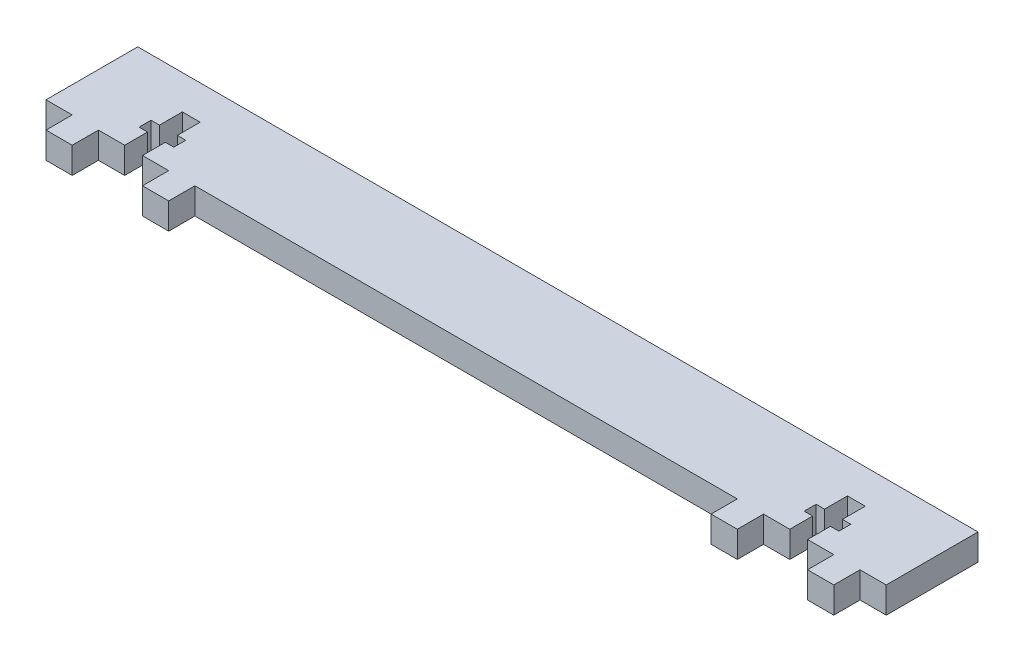
SolidWorks part; units mm, degrees
ref_plane "Front Plane" through (0, 0, 0) normal (0, 0, 1) x (1, 0, 0)
ref_plane "Top Plane" through (0, 0, 0) normal (0, 1, 0) x (1, 0, 0)
ref_plane "Right Plane" through (0, 0, 0) normal (1, 0, 0) x (0, 0, -1)
sketch "Sketch1" plane through (0, 0, 0) normal (0, 1, 0) x (1, 0, 0)
  line L0 (0, 11.1125) -> (0, -11.1125) construction
  line L1 (-101.7524, -11.1125) -> (-95.4024, -11.1125)
  line L2 (-101.7524, -11.1125) -> (-101.7524, 11.1125)
  line L3 (-101.7524, 11.1125) -> (101.7524, 11.1125)
  line L4 (101.7524, -11.1125) -> (101.7524, 11.1125)
  line L5 (-101.7524, -11.1125) -> (101.7524, 11.1125) construction
  line L6 (-101.7524, 11.1125) -> (101.7524, -11.1125) construction
  line L7 (-65.6844, -11.1125) -> (65.6844, -11.1125)
  line L8 (101.7524, -11.1125) -> (95.4024, -11.1125)
  point P0 (0, 0)
  line B0 (-89.0524, -11.1125) -> (-89.0524, -17.4625)
  line B1 (-89.0524, -17.4625) -> (-95.4024, -17.4625)
  line B2 (-95.4024, -17.4625) -> (-95.4024, -11.1125)
  line B3 (-82.7024, -11.1125) -> (-82.7024, -5.5775)
  line B4 (-82.7024, -5.5775) -> (-84.7434, -5.5775)
  line B5 (-84.7434, -5.5775) -> (-84.7434, -2.6775)
  line B6 (-84.7434, -2.6775) -> (-82.7024, -2.6775)
  line B7 (-82.7024, -2.6775) -> (-82.7024, 2.8575)
  line B8 (-82.7024, 2.8575) -> (-78.3844, 2.8575)
  line B9 (-78.3844, 2.8575) -> (-78.3844, -2.6775)
  line B10 (-78.3844, -2.6775) -> (-76.3434, -2.6775)
  line B11 (-76.3434, -2.6775) -> (-76.3434, -5.5775)
  line B12 (-76.3434, -5.5775) -> (-78.3844, -5.5775)
  line B13 (-78.3844, -5.5775) -> (-78.3844, -11.1125)
  line B14 (-80.5434, 2.8575) -> (-80.5434, -11.1125) construction
  line B15 (-72.0344, -11.1125) -> (-78.3844, -11.1125)
  line B16 (-65.6844, -17.4625) -> (-65.6844, -11.1125)
  line B17 (-89.0524, -11.1125) -> (-82.7024, -11.1125)
  line B18 (-72.0344, -17.4625) -> (-65.6844, -17.4625)
  line B19 (-72.0344, -11.1125) -> (-72.0344, -17.4625)
  line B20 (89.0524, -11.1125) -> (89.0524, -17.4625)
  line B21 (89.0524, -17.4625) -> (95.4024, -17.4625)
  line B22 (95.4024, -17.4625) -> (95.4024, -11.1125)
  line B23 (82.7024, -11.1125) -> (82.7024, -5.5775)
  line B24 (82.7024, -5.5775) -> (84.7434, -5.5775)
  line B25 (84.7434, -5.5775) -> (84.7434, -2.6775)
  line B26 (84.7434, -2.6775) -> (82.7024, -2.6775)
  line B27 (82.7024, -2.6775) -> (82.7024, 2.8575)
  line B28 (82.7024, 2.8575) -> (78.3844, 2.8575)
  line B29 (78.3844, 2.8575) -> (78.3844, -2.6775)
  line B30 (78.3844, -2.6775) -> (76.3434, -2.6775)
  line B31 (76.3434, -2.6775) -> (76.3434, -5.5775)
  line B32 (76.3434, -5.5775) -> (78.3844, -5.5775)
  line B33 (78.3844, -5.5775) -> (78.3844, -11.1125)
  line B34 (80.5434, 2.8575) -> (80.5434, -11.1125) construction
  line B35 (72.0344, -11.1125) -> (78.3844, -11.1125)
  line B36 (65.6844, -17.4625) -> (65.6844, -11.1125)
  line B37 (89.0524, -11.1125) -> (82.7024, -11.1125)
  line B38 (72.0344, -17.4625) -> (65.6844, -17.4625)
  line B39 (72.0344, -11.1125) -> (72.0344, -17.4625)
  dimension "D1" = 22.225
  dimension "D2" = 131.3688
  dimension "D3" = 6.35
sketch_block_instance "Male T-slot assembly-1"
sketch_block "Male T-slot assembly" parameters "D1"=6.35, "D2"=6.35, "D3"=4.318, "D4"=2.9, "D5"=8.4, "D6"=13.97, "D7"=6.35
sketch_block_instance "Male T-slot assembly-3"
extrude "Boss-Extrude1" add sketch "Sketch1" along normal blind 6.35 contours B39 B35 B33 B32 B31 B30 B29 B28 B27 B26 B25 B24 B23 B37 B20 B21 B22 L8 L4 L3 L2 L1 B2 B1 B0 B17 B3 B4 B5 B6 B7 B8 B9 B10 B11 B12 B13 B15 B19 B18 B16 L7 B36 B38 region at (0, 0, 0.3764)
equation "\"Ball Diameter\"= 1.75in"
equation "\"Ball Radius\" = \"Ball Diameter\"/2"
equation "\"Sheet Thickness\"= 0.25in"
equation "\"Screw Diameter\"= .17in"
equation "\"Robot Diameter\"= 14in"
equation "\"Castor Screw Diameter\"= 0.22in"
equation "\"Wheel Diameter\" = 4in"
equation "\"Nut Diameter\" = 8.4mm"
equation "\"Nut Height\" = 2.9mm"
equation "\"Screw Height\" = 0.55in"
equation "\"Pulley Diameter\" = 1in"
equation "\"Reactor Height\" = 14in"
equation "\"Elevator Height\" = 11.5in"
equation "\"Elevator Width\" = \"Ball Diameter\" + 0.25in"
equation "\"Elevator Bearing Diameter\" = sqr(2*(\"Sheet Thickness\"^2)) + 0.2in"
equation "\"Elevator Axle Endcap Diameter\" = \"Pulley Diameter\" + 0.25in"
equation "\"Elevator Axle Length\" = \"Elevator Width\" + 8*\"Sheet Thickness\""
equation "\"Elevator Clearance from Axis\" = 3.5in"
equation "\"Elevator Horizontal Clearance\" = \"Elevator Width\" + 0.5in"
equation "\"Claw Horizontal Seperation\" = (\"Elevator Width\"/2) - (1.5 * \"Sheet Thickness\") - 0.15in"
equation "\"Claw Radius\" = \"Ball Radius\" + 0.1in"
equation "\"Castor Wheel Height\" = 1.25in"
equation "\"Length of Chute\" = 8in"
equation "\"D1@Sketch1\"=\"Ball Radius\""
